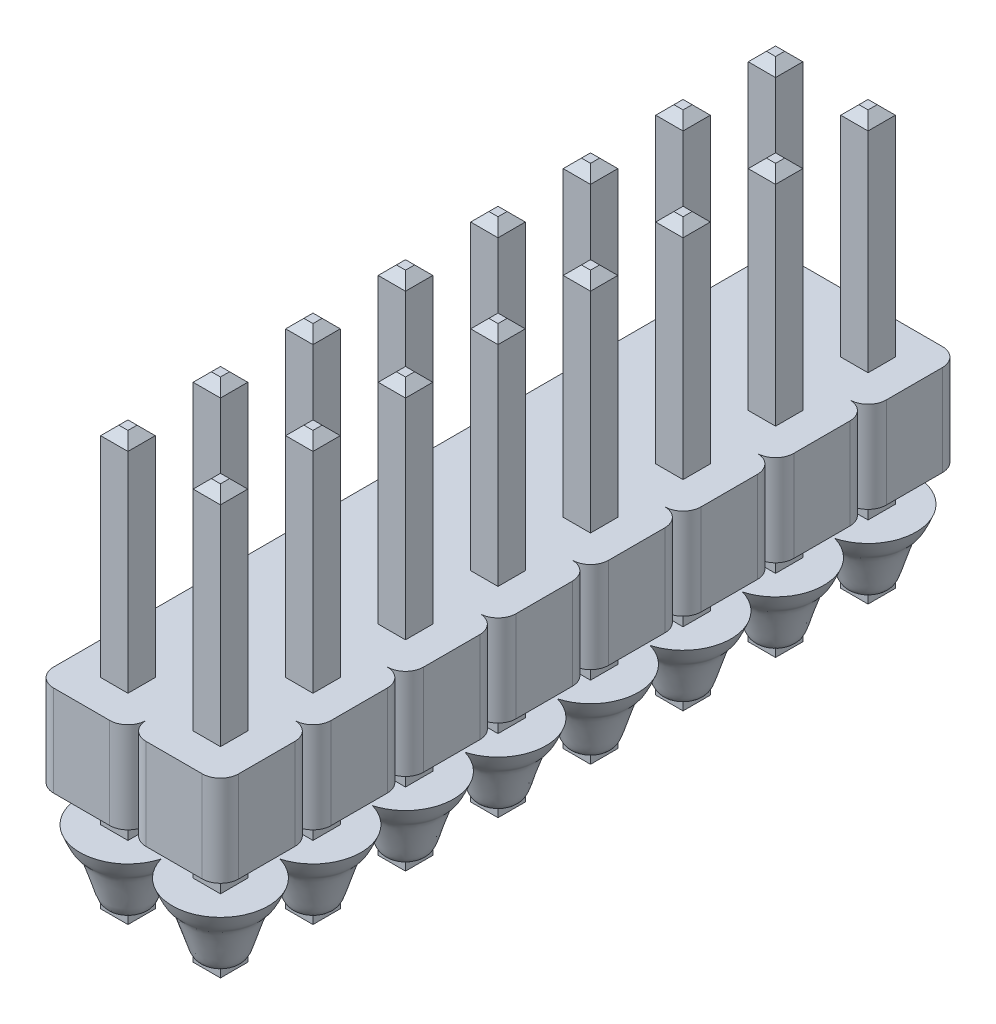
SolidWorks part; units mm, degrees
note: '?' marks a value the reader was unsure of.
ref_plane "Front Plane" through (0, 0, 0) normal (0, 0, 1) x (1, 0, 0)
ref_plane "Top Plane" through (0, 0, 0) normal (0, 1, 0) x (1, 0, 0)
ref_plane "Right Plane" through (0, 0, 0) normal (1, 0, 0) x (0, 0, -1)
ref_plane "Plane1" through (0, 0, 0) normal (0, 1, 0) x (-1, 0, 0)
sketch "Sketch1" plane through (0, 0, 0) normal (0, 1, 0) x (-1, 0, 0)
  line L0 (-0.77, 1.27) -> (0.77, 1.27)
  line L1 (1.27, 0.77) -> (1.27, -0.77)
  line L2 (0.77, -1.27) -> (-0.77, -1.27)
  line L3 (-1.27, -0.77) -> (-1.27, 0.77)
  line L4 (-0.77, 0.77) -> (0.77, -0.77) construction
  arc A0 (1.27, 0.77) -> (0.77, 1.27) centre (0.77, 0.77) ccw
  arc A1 (0.77, -1.27) -> (1.27, -0.77) centre (0.77, -0.77) ccw
  arc A2 (-1.27, -0.77) -> (-0.77, -1.27) centre (-0.77, -0.77) ccw
  arc A3 (-0.77, 1.27) -> (-1.27, 0.77) centre (-0.77, 0.77) ccw
  dimension "D3" = 0.5
  dimension "D2" = 2.54
extrude "Boss-Extrude1" add sketch "Sketch1" along normal blind 2.5
ref_plane "Plane2" through (0.77, 0, 1.27) normal (-1, 0, 0) x (0, 0, 1)
ref_plane "Plane3" through (0.77, 0, 1.27) normal (0, -1, 0) x (0, 0, 1)
ref_axis "Axis1" through (0.77, 0, -79.63) along (0, 0, 1)?
pattern_linear "LPattern1" count 8 spacing 2.54 along (0, 0, 1) count 2 spacing 2.54 along (1, 0, 0) of "Boss-Extrude1"
ref_plane "Plane4" through (0, 0, 0) normal (0, 1, 0) x (-1, 0, 0)
sketch "Sketch2" plane through (0, 0, 0) normal (0, 1, 0) x (-1, 0, 0)
  line L0 (-0.375, 0.375) -> (0.375, 0.375)
  line L1 (0.375, 0.375) -> (0.375, -0.375)
  line L2 (0.375, -0.375) -> (-0.375, -0.375)
  line L3 (-0.375, -0.375) -> (-0.375, 0.375)
  line L4 (-0.375, 0.375) -> (0.375, -0.375) construction
  dimension "D1" = 0.75
extrude "Boss-Extrude2" add sketch "Sketch2" along normal blind 8.5 and the other way blind 3.25
ref_plane "Plane5" through (0.3725, 0, 0.3725) normal (-1, 0, 0) x (0, 0, 1)
ref_plane "Plane6" through (0.3725, 0, 0.3725) normal (0, -1, 0) x (0, 0, 1)
ref_axis "Axis2" through (0.3725, 0, -80.5275) along (0, 0, 1)?
chamfer "Chamfer1" distance 0.25 angle 45 8 edges at (0, -3.25, 0.375) (-0.375, -3.25, 0) (0.375, -3.25, 0) (0, -3.25, -0.375) (0, 8.5, 0.375) (-0.375, 8.5, 0) (0, 8.5, -0.375) (0.375, 8.5, 0)
pattern_linear "LPattern2" count 8 spacing 2.54 along (0, 0, 1) count 2 spacing 2.54 along (1, 0, 0) of "Boss-Extrude2", "Chamfer1"
ref_axis "Axis3" through (0, -3.575, 0) along (0, 1, 0)?
ref_plane "Plano1" through (0, 0, 0) normal (0, 0, -1) x (-1, 0, 0)
sketch "Esboço1" plane through (0, 0, 0) normal (0, 0, -1) x (-1, 0, 0)
  line L0 (0, -3.2042) -> (0, 0) construction
  line L5 (-1.3202, -1) -> (0, -1)
  line L7 (0, -3) -> (0, -1)
  spline S0 degree 3 poles (0, -3) (-0.5454, -2.8051) (-0.5467, -2.8967) (-1.0377, -1.239) (-1.0444, -1.7094) (-1.3202, -1) knots 0 0 0 0 0.39982 0.605693 1 1 1 1
  dimension "D1" = 2
  dimension "D2" = 1
revolve "Revolução2" add sketch "Esboço1" angle 360 about L0
pattern_linear "Padrão linear1" count 8 spacing 2.54 along (0, 0, 1) count 2 spacing 2.54 along (1, 0, 0) of "Revolução2"
